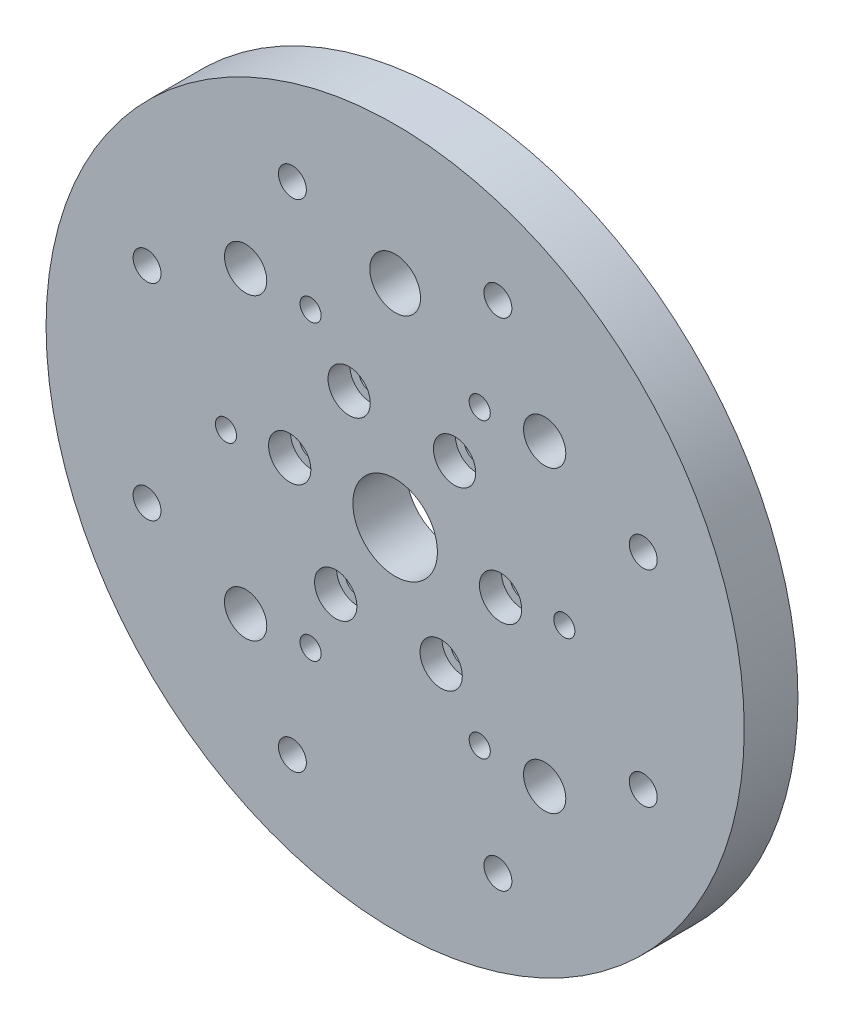
SolidWorks part; units mm, degrees
material "Aleación 6061"
ref_plane "Alzado" through (0, 0, 0) normal (0, 0, 1) x (1, 0, 0)
ref_plane "Planta" through (0, 0, 0) normal (0, 1, 0) x (1, 0, 0)
ref_plane "Vista lateral" through (0, 0, 0) normal (1, 0, 0) x (0, 0, -1)
sketch "Croquis1" plane through (0, 0, 0) normal (0, 0, 1) x (1, 0, 0)
  circle A0 centre (152.4, 0) radius 41.275
  dimension "D1" = 82.55
  dimension "D2" = 152.4
extrude "Brida_D3-25in_1-4in" add sketch "Croquis1" along normal blind 6.35 from offset 413.9
sketch "Croquis2" plane through (0, 0, 0) normal (0, 0, 1) x (1, 0, 0)
  circle A0 centre (159.426, 10.3385) radius 1.45
  circle A1 centre (146.9596, 11.254) radius 1.45
  circle A2 centre (139.9336, 0.9155) radius 1.45
  circle A3 centre (145.374, -10.3385) radius 1.45
  circle A4 centre (157.8404, -11.254) radius 1.45
  circle A5 centre (164.8664, -0.9155) radius 1.45
  circle A6 centre (152.4, 0) radius 5
  dimension "D1" = 2.9
  dimension "D2" = 2.9
  dimension "D3" = 2.9
  dimension "D4" = 2.9
  dimension "D5" = 2.9
  dimension "D6" = 2.9
  dimension "D7" = 10
  dimension "D8" = 159.426
  dimension "D9" = 10.3385
  dimension "D10" = 146.9596
  dimension "D11" = 11.254
  dimension "D12" = 139.9336
  dimension "D13" = 0.9155
  dimension "D14" = 145.374
  dimension "D15" = 10.3385
  dimension "D16" = 157.8404
  dimension "D17" = 11.254
  dimension "D18" = 164.8664
  dimension "D19" = 0.9155
  dimension "D20" = 152.4
extrude "Barrenos_salida_M6" cut sketch "Croquis2" along normal blind 6.35 from offset 413.9
sketch "Croquis3" plane through (0, 0, 0) normal (0, 0, 1) x (1, 0, 0)
  circle A0 centre (159.426, 10.3385) radius 2.5
  circle A1 centre (146.9596, 11.254) radius 2.5
  circle A2 centre (139.9336, 0.9155) radius 2.5
  circle A3 centre (145.374, -10.3385) radius 2.5
  circle A4 centre (157.8404, -11.254) radius 2.5
  circle A5 centre (164.8664, -0.9155) radius 2.5
  dimension "D1" = 5
  dimension "D2" = 5
  dimension "D3" = 5
  dimension "D4" = 5
  dimension "D5" = 5
  dimension "D6" = 5
  dimension "D7" = 159.426
  dimension "D8" = 10.3385
  dimension "D9" = 146.9596
  dimension "D10" = 11.254
  dimension "D11" = 139.9336
  dimension "D12" = 0.9155
  dimension "D13" = 145.374
  dimension "D14" = 10.3385
  dimension "D15" = 157.8404
  dimension "D16" = 11.254
  dimension "D17" = 164.8664
  dimension "D18" = 0.9155
extrude "Refrentado_M2-5" cut sketch "Croquis3" along normal blind 2.6 from offset 417.65
sketch "Croquis4" plane through (0, 0, 0) normal (0, 0, 1) x (1, 0, 0)
  circle A0 centre (170.0777, 17.6777) radius 2.5
  circle A1 centre (134.7223, 17.6777) radius 2.5
  circle A2 centre (134.7223, -17.6777) radius 2.5
  circle A3 centre (170.0777, -17.6777) radius 2.5
  circle A4 centre (152.4, 25) radius 3
  dimension "D1" = 5
  dimension "D2" = 5
  dimension "D3" = 5
  dimension "D4" = 5
  dimension "D5" = 6
  dimension "D6" = 170.0777
  dimension "D7" = 17.6777
  dimension "D8" = 134.7223
  dimension "D9" = 17.6777
  dimension "D10" = 134.7223
  dimension "D11" = 17.6777
  dimension "D12" = 170.0777
  dimension "D13" = 17.6777
  dimension "D14" = 152.4
  dimension "D15" = 25
extrude "ISO9409-50_4xM6_y_pasador_D6" cut sketch "Croquis4" along normal blind 6.35 from offset 413.9
sketch "Croquis5" plane through (0, 0, 0) normal (0, 0, 1) x (1, 0, 0)
  circle A0 centre (181.7332, 12.1502) radius 1.65
  circle A1 centre (164.5502, 29.3332) radius 1.65
  circle A2 centre (140.2498, 29.3332) radius 1.65
  circle A3 centre (123.0668, 12.1502) radius 1.65
  circle A4 centre (123.0668, -12.1502) radius 1.65
  circle A5 centre (140.2498, -29.3332) radius 1.65
  circle A6 centre (164.5502, -29.3332) radius 1.65
  circle A7 centre (181.7332, -12.1502) radius 1.65
  dimension "D1" = 3.3
  dimension "D2" = 3.3
  dimension "D3" = 3.3
  dimension "D4" = 3.3
  dimension "D5" = 3.3
  dimension "D6" = 3.3
  dimension "D7" = 3.3
  dimension "D8" = 3.3
  dimension "D9" = 181.7332
  dimension "D10" = 12.1502
  dimension "D11" = 164.5502
  dimension "D12" = 29.3332
  dimension "D13" = 140.2498
  dimension "D14" = 29.3332
  dimension "D15" = 123.0668
  dimension "D16" = 12.1502
  dimension "D17" = 123.0668
  dimension "D18" = 12.1502
  dimension "D19" = 140.2498
  dimension "D20" = 29.3332
  dimension "D21" = 164.5502
  dimension "D22" = 29.3332
  dimension "D23" = 181.7332
  dimension "D24" = 12.1502
extrude "Patron_8xM4_PCD2-5in" cut sketch "Croquis5" along normal blind 6.35 from offset 413.9
sketch "Croquis6" plane through (0, 0, 0) normal (0, 0, 1) x (1, 0, 0)
  circle A0 centre (172.4, 0) radius 1.25
  circle A1 centre (162.4, 17.3205) radius 1.25
  circle A2 centre (142.4, 17.3205) radius 1.25
  circle A3 centre (132.4, 0) radius 1.25
  circle A4 centre (142.4, -17.3205) radius 1.25
  circle A5 centre (162.4, -17.3205) radius 1.25
  dimension "D1" = 2.5
  dimension "D2" = 2.5
  dimension "D3" = 2.5
  dimension "D4" = 2.5
  dimension "D5" = 2.5
  dimension "D6" = 2.5
  dimension "D7" = 172.4
  dimension "D8" = 162.4
  dimension "D9" = 17.3205
  dimension "D10" = 142.4
  dimension "D11" = 17.3205
  dimension "D12" = 132.4
  dimension "D13" = 142.4
  dimension "D14" = 17.3205
  dimension "D15" = 162.4
  dimension "D16" = 17.3205
extrude "Patron_6xM3_PCD40" cut sketch "Croquis6" along normal blind 6.35 from offset 413.9
ref_plane "Plano_xJ3" through (152.4, 0, 0) normal (1, 0, 0) x (0, 0, -1)
ref_plane "Plano_zJ5" through (0, 0, 336.55) normal (0, 0, 1) x (1, 0, 0)
ref_axis "Eje_J6" through (152.4, 0, 420.5675) along (0, 0, -1)
